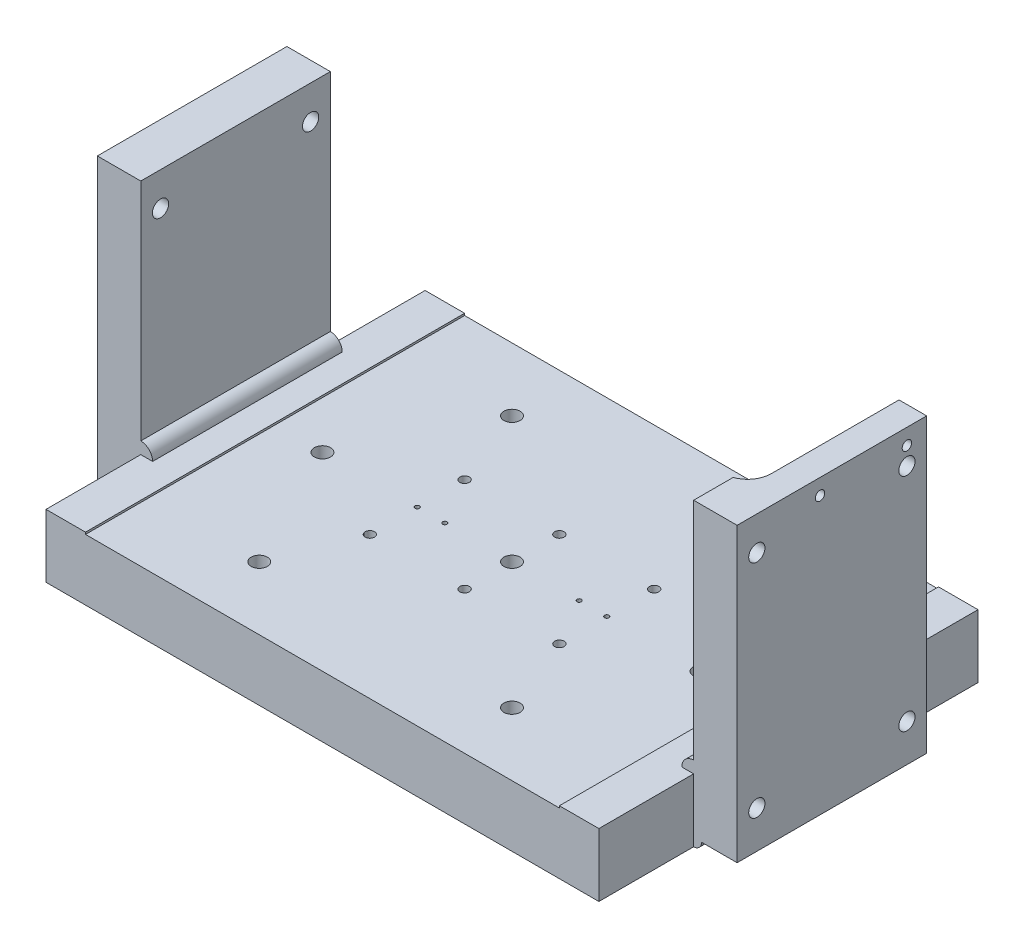
SolidWorks part; units mm, degrees
material "6061 Alloy"
ref_plane "Front" through (0, 0, 0) normal (0, 0, 1) x (1, 0, 0)
ref_plane "Top" through (0, 0, 0) normal (0, 1, 0) x (1, 0, 0)
ref_plane "Right" through (0, 0, 0) normal (1, 0, 0) x (0, 0, -1)
sketch "Sketch1" plane through (0, 0, 0) normal (0, 1, 0) x (1, 0, 0)
  line L0 (-111.125, -76.2) -> (111.125, 76.2) construction
  line L1 (-111.125, 76.2) -> (111.125, 76.2)
  line L2 (-111.125, 76.2) -> (-111.125, -76.2)
  line L3 (-111.125, -76.2) -> (111.125, -76.2)
  line L4 (111.125, 76.2) -> (111.125, -76.2)
  dimension "D1" = 222.25
  dimension "D2" = 152.4
extrude "Extrude1" add sketch "Sketch1" along normal blind 25.4
ref_plane "Plane1" through (0, 3.175, 0) normal (0, 1, 0) x (-1, 0, 0)
sketch "Sketch2" plane through (0, 3.175, 0) normal (0, 1, 0) x (-1, 0, 0)
  line L0 (111.125, -76.2) -> (111.125, 76.2) construction
  line L1 (111.125, 38.1) -> (128.5875, 38.1)
  line L2 (111.125, 38.1) -> (111.125, -38.1)
  line L3 (111.125, -38.1) -> (128.5875, -38.1)
  line L4 (128.5875, 38.1) -> (128.5875, -38.1)
  line L5 (-111.125, 76.2) -> (-111.125, -76.2) construction
  line L6 (-111.125, 38.1) -> (-128.5875, 38.1)
  line L7 (-111.125, 38.1) -> (-111.125, -38.1)
  line L8 (-111.125, -38.1) -> (-128.5875, -38.1)
  line L9 (-128.5875, 38.1) -> (-128.5875, -38.1)
  line L10 (111.125, 76.2) -> (-111.125, 76.2) construction
  dimension "D1" = 76.2
  dimension "D2" = 38.1
  dimension "D3" = 257.175
extrude "Extrude2" add sketch "Sketch2" along normal blind 117.475
sketch "Sketch5" plane through (0, 25.4, 0) normal (0, 1, 0) x (-1, 0, 0)
  line L0 (111.125, 76.2) -> (-111.125, 76.2) construction
  line L1 (95.25, 76.2) -> (-95.25, 76.2)
  line L2 (95.25, 76.2) -> (95.25, -76.2)
  line L3 (95.25, -76.2) -> (-95.25, -76.2)
  line L4 (-95.25, 76.2) -> (-95.25, -76.2)
  line L5 (-111.125, -76.2) -> (111.125, -76.2) construction
  line L6 (111.125, 38.1) -> (111.125, 76.2) construction
  dimension "D1" = 190.5
  dimension "D2" = 15.875
extrude "Cut-Extrude1" cut sketch "Sketch5" against normal blind 0.7937
hole_wizard "5/16-18 Tapped Hole1" positions "Sketch4" profile "Sketch3" tap size "5/16-18" standard "Ansi Inch"
sketch "Sketch4" plane through (128.5875, 0, 0) normal (1, 0, 0) x (0, 0, -1)
  line L1 (-76.2, 24.6062) -> (76.2, 24.6062) construction
  line L2 (-76.2, 25.4) -> (-76.2, 0) construction
  point P0 (-30.1625, 107.1562)
  point P1 (-30.1625, 18.2563)
  point P3 (30.1625, 18.2563)
  point P5 (30.1625, 107.1562)
  dimension "D1" = 88.9
  dimension "D2" = 60.325
  dimension "D4" = 6.35
  dimension "D5" = 46.0375
cosmetic thread "Hole Thread1" parameters "D1"=15.875, "D2"=7.9375
cosmetic thread "Hole Thread2" parameters "D1"=15.875, "D2"=7.9375
cosmetic thread "Hole Thread3" parameters "D1"=15.875, "D2"=7.9375
cosmetic thread "Hole Thread4" parameters "D1"=15.875, "D2"=7.9375
sketch "Sketch3" plane through (128.5875, 107.1562, 30.1625) normal (0, 1, 0) x (0, 0, -1)
  line L0 (0, 0) -> (0, 24.8846)
  line L1 (0, 24.8846) -> (3.2639, 22.9235)
  line L2 (3.2639, 22.9235) -> (3.2639, 0)
  line L5 (3.2639, 0) -> (0, 0)
  line L10 (0, 24.8846) -> (-3.2639, 22.9235) construction
  line L11 (0, -6.35) -> (0, 107.95) construction
  dimension "Tap Drill Dia." = 6.5278
  dimension "Tap Drill Depth" = 22.9235
  dimension "Drill Angle" = 118
hole_wizard "5/16-18 Tapped Hole2" positions "Sketch7" profile "Sketch6" tap size "5/16-18" standard "Ansi Inch"
sketch "Sketch7" plane through (-128.5875, 0, 0) normal (-1, 0, 0) x (0, 0, 1)
  point P1 (30.1625, 107.1562)
  point P4 (-30.1625, 107.1562)
  point P7 (-30.1625, 18.2563)
  point P10 (30.1625, 18.2562)
sketch "Sketch6" plane through (-128.5875, 107.1562, 30.1625) normal (0, 1, 0) x (0, 0, 1)
  line L0 (0, 0) -> (0, 24.8846)
  line L1 (0, 24.8846) -> (3.2639, 22.9235)
  line L2 (3.2639, 22.9235) -> (3.2639, 0)
  line L5 (3.2639, 0) -> (0, 0)
  line L10 (0, 24.8846) -> (-3.2639, 22.9235) construction
  line L11 (0, -6.35) -> (0, 107.95) construction
  dimension "Tap Drill Dia." = 6.5278
  dimension "Tap Drill Depth" = 22.9235
  dimension "Drill Angle" = 118
cosmetic thread "Hole Thread5" parameters "D1"=15.875, "D2"=7.9375
cosmetic thread "Hole Thread6" parameters "D1"=15.875, "D2"=7.9375
cosmetic thread "Hole Thread7" parameters "D1"=15.875, "D2"=7.9375
cosmetic thread "Hole Thread8" parameters "D1"=15.875, "D2"=7.9375
sketch "Sketch9" plane through (0, 0, 0) normal (0, 0, 1) x (1, 0, 0)
  circle A0 centre (-111.125, 25.4) radius 4.7625
  circle A1 centre (-111.125, 3.175) radius 3.175
  circle A2 centre (111.125, 3.175) radius 3.175
  circle A3 centre (111.125, 25.4) radius 4.7625
  dimension "D1" = 9.525
extrude "Extrude3" add sketch "Sketch9" along normal mid plane 76.2
hole_wizard "5/16-18 Tapped Hole3" positions "Sketch11" profile "Sketch10" tap size "5/16-18" standard "Ansi Inch" end condition through all
sketch "Sketch11" plane through (0, 24.6062, 0) normal (0, 1, 0) x (-1, 0, 0)
  point P0 (0, 0)
  point P1 (50.8, -50.8)
  point P3 (50.8, 50.8)
  point P5 (-50.8, 50.8)
  point P7 (-50.8, -50.8)
  point P11 (76.2, 0)
  point P13 (-76.2, 0)
  dimension "D1" = 101.6
  dimension "D2" = 101.6
  dimension "D3" = 50.8
  dimension "D4" = 50.8
  dimension "D5" = 76.2
  dimension "D6" = 152.4
sketch "Sketch10" plane through (0, 24.6062, 0) normal (1, 0, 0) x (0, 0, 1)
  line L0 (0, 0) -> (0, 24.6062)
  line L1 (0, 24.6062) -> (3.2639, 24.6062)
  line L2 (3.2639, 24.6062) -> (3.2639, 0)
  line L5 (3.2639, 0) -> (0, 0)
  line L11 (0, -6.35) -> (0, 107.95) construction
  dimension "Thru Tap Drill Dia." = 6.5278
  dimension "Thru Tap Drill Depth" = 24.6062
cosmetic thread "Hole Thread9" parameters "D2"=7.9375
cosmetic thread "Hole Thread10" parameters "D2"=7.9375
cosmetic thread "Hole Thread11" parameters "D2"=7.9375
cosmetic thread "Hole Thread12" parameters "D2"=7.9375
cosmetic thread "Hole Thread13" parameters "D2"=7.9375
cosmetic thread "Hole Thread20" parameters "D2"=7.9375
cosmetic thread "Hole Thread21" parameters "D2"=7.9375
hole_wizard "#10-24 Tapped Hole2" positions "Sketch13" profile "Sketch12" tap size "#10-24" standard "Ansi Inch" end condition through all
sketch "Sketch13" plane through (0, 24.6062, 0) normal (0, 1, 0) x (-1, 0, 0)
  point P0 (38.1, 19.05)
  point P1 (38.1, -19.05)
  point P3 (0, -19.05)
  point P5 (0, 19.05)
  point P7 (-38.1, 19.05)
  point P9 (-38.1, -19.05)
  dimension "D1" = 19.05
  dimension "D2" = 38.1
  dimension "D3" = 76.2
  dimension "D4" = 38.1
sketch "Sketch12" plane through (-38.1, 24.6062, 19.05) normal (1, 0, 0) x (0, 0, 1)
  line L0 (0, 0) -> (0, 24.6062)
  line L1 (0, 24.6062) -> (1.8986, 24.6062)
  line L2 (1.8986, 24.6062) -> (1.8986, 0)
  line L5 (1.8986, 0) -> (0, 0)
  line L11 (0, -6.35) -> (0, 107.95) construction
  dimension "Thru Tap Drill Dia." = 3.7973
  dimension "Thru Tap Drill Depth" = 24.6062
cosmetic thread "Hole Thread14" parameters "D2"=4.826
cosmetic thread "Hole Thread15" parameters "D2"=4.826
cosmetic thread "Hole Thread16" parameters "D2"=4.826
cosmetic thread "Hole Thread17" parameters "D2"=4.826
cosmetic thread "Hole Thread18" parameters "D2"=4.826
cosmetic thread "Hole Thread19" parameters "D2"=4.826
hole_wizard "1/4-20 Tapped Hole1" positions "Sketch15" profile "Sketch14" tap size "1/4-20" standard "ANSI Inch"
sketch "Sketch15" plane through (-111.125, 0, 0) normal (-1, 0, 0) x (0, 0, 1)
  line L0 (-76.2, 0) -> (-38.1, 0) construction
  line L1 (-76.2, 25.4) -> (-76.2, 0) construction
  point P0 (-68.2625, 12.7)
  point P6 (-68.2625, 20.6375)
  dimension "D1" = 12.7
  dimension "D2" = 7.9375
  dimension "D3" = 7.9375
sketch "Sketch14" plane through (-111.125, 12.7, -68.2625) normal (0, 1, 0) x (0, 0, 1)
  line L0 (0, 0) -> (0, 18.0438)
  line L1 (0, 18.0438) -> (2.5527, 16.51)
  line L2 (2.5527, 16.51) -> (2.5527, 0)
  line L5 (2.5527, 0) -> (0, 0)
  line L10 (0, 18.0438) -> (-2.5527, 16.51) construction
  line L11 (0, -6.35) -> (0, 107.95) construction
  dimension "Tap Drill Dia." = 5.1054
  dimension "Tap Drill Depth" = 16.51
  dimension "Drill Angle" = 118
cosmetic thread "Hole Thread22" parameters "D1"=12.7, "D2"=6.35
cosmetic thread "Hole Thread29" parameters "D1"=12.7, "D2"=6.35
hole_wizard "#2-56 Tapped Hole1" positions "Sketch17" profile "Sketch16" tap size "#2-56" standard "Ansi Inch"
sketch "Sketch17" plane through (0, 24.6062, 0) normal (0, 1, 0) x (-1, 0, 0)
  circle A0 centre (-38.1, 19.05) radius 1.8986 construction
  point P0 (38.1, 0)
  point P1 (26.9875, 0)
  point P6 (-38.1, 0)
  point P8 (-26.9875, 0)
  dimension "D2" = 11.1125
  dimension "D1" = 11.1125
sketch "Sketch16" plane through (-38.1, 24.6062, 0) normal (1, 0, 0) x (0, 0, 1)
  line L0 (0, 0) -> (0, 7.1382)
  line L1 (0, 7.1382) -> (0.889, 6.604)
  line L2 (0.889, 6.604) -> (0.889, 0)
  line L5 (0.889, 0) -> (0, 0)
  line L10 (0, 7.1382) -> (-0.889, 6.604) construction
  line L11 (0, -6.35) -> (0, 107.95) construction
  dimension "Tap Drill Dia." = 1.778
  dimension "Tap Drill Depth" = 6.604
  dimension "Drill Angle" = 118
cosmetic thread "Hole Thread23" parameters "D1"=4.318, "D2"=2.1844
cosmetic thread "Hole Thread24" parameters "D1"=4.318, "D2"=2.1844
cosmetic thread "Hole Thread27" parameters "D1"=4.318, "D2"=2.1844
cosmetic thread "Hole Thread28" parameters "D1"=4.318, "D2"=2.1844
hole_wizard "#10-24 Tapped Hole3" positions "Sketch19" profile "Sketch20" tap size "#10-24" standard "Ansi Inch" end condition up to next
sketch "Sketch19" plane through (128.5875, 0, 0) normal (1, 0, 0) x (0, 0, -1)
  point P0 (-4.7625, 114.3)
  point P1 (30.1625, 114.3)
  dimension "D1" = 34.925
  dimension "D2" = 7.1437
sketch "Sketch20" plane through (128.5875, 114.3, 4.7625) normal (0, 1, 0) x (0, 0, -1)
  line L0 (0, 0) -> (0, 17.4625)
  line L1 (0, 17.4625) -> (1.8986, 17.4625)
  line L2 (1.8986, 17.4625) -> (1.8986, 0)
  line L5 (1.8986, 0) -> (0, 0)
  line L11 (0, -6.35) -> (0, 107.95) construction
  dimension "Thru Tap Drill Dia." = 3.7973
  dimension "Thru Tap Drill Depth" = 17.4625
cosmetic thread "Hole Thread25" parameters "D2"=4.826
cosmetic thread "Hole Thread26" parameters "D2"=4.826
sketch "Sketch21" plane through (111.125, 0, 0) normal (-1, 0, 0) x (0, 0, 1)
  line L1 (-38.1, 120.65) -> (22.225, 120.65)
  line L2 (-38.1, 120.65) -> (-38.1, 107.95)
  line L3 (-38.1, 107.95) -> (22.225, 107.95)
  line L4 (22.225, 120.65) -> (22.225, 107.95)
  dimension "D1" = 60.325
  dimension "D2" = 12.7
extrude "Cut-Extrude2" cut sketch "Sketch21" against normal blind 6.35
fillet "Fillet1" radius 9.525 1 edges at (117.475, 114.3, 22.225)
hole_wizard "CBORE for 1/4 Socket Head Cap Screw1" positions "Sketch23" profile "Sketch22" counterbore size "1/4" standard "Ansi Inch" end condition up to next
sketch "Sketch23" plane through (0, 0, 0) normal (0, -1, 0) x (1, 0, 0)
  point P1 (-50.8, 50.8)
  point P4 (50.8, 50.8)
  point P7 (50.8, -50.8)
  point P10 (0, 0)
  point P13 (-50.8, -50.8)
  point P16 (-76.2, 0)
  point P19 (76.2, 0)
sketch "Sketch22" plane through (-50.8, 0, 50.8) normal (1, 0, 0) x (0, 0, -1)
  line L0 (0, 0) -> (0, 120.65)
  line L1 (0, 120.65) -> (3.2639, 120.65)
  line L3 (3.2639, 120.65) -> (3.2639, 7.112)
  line L4 (3.2639, 7.112) -> (5.5562, 7.112)
  line L5 (5.5562, 7.112) -> (5.5562, 0)
  line L7 (5.5562, 0) -> (0, 0)
  line L11 (0, -6.35) -> (0, 107.95) construction
  dimension "Thru Hole Dia." = 6.5278
  dimension "Thru Hole Depth" = 120.65
  dimension "C'Bore Dia." = 11.1125
  dimension "C'Bore Depth" = 7.112
